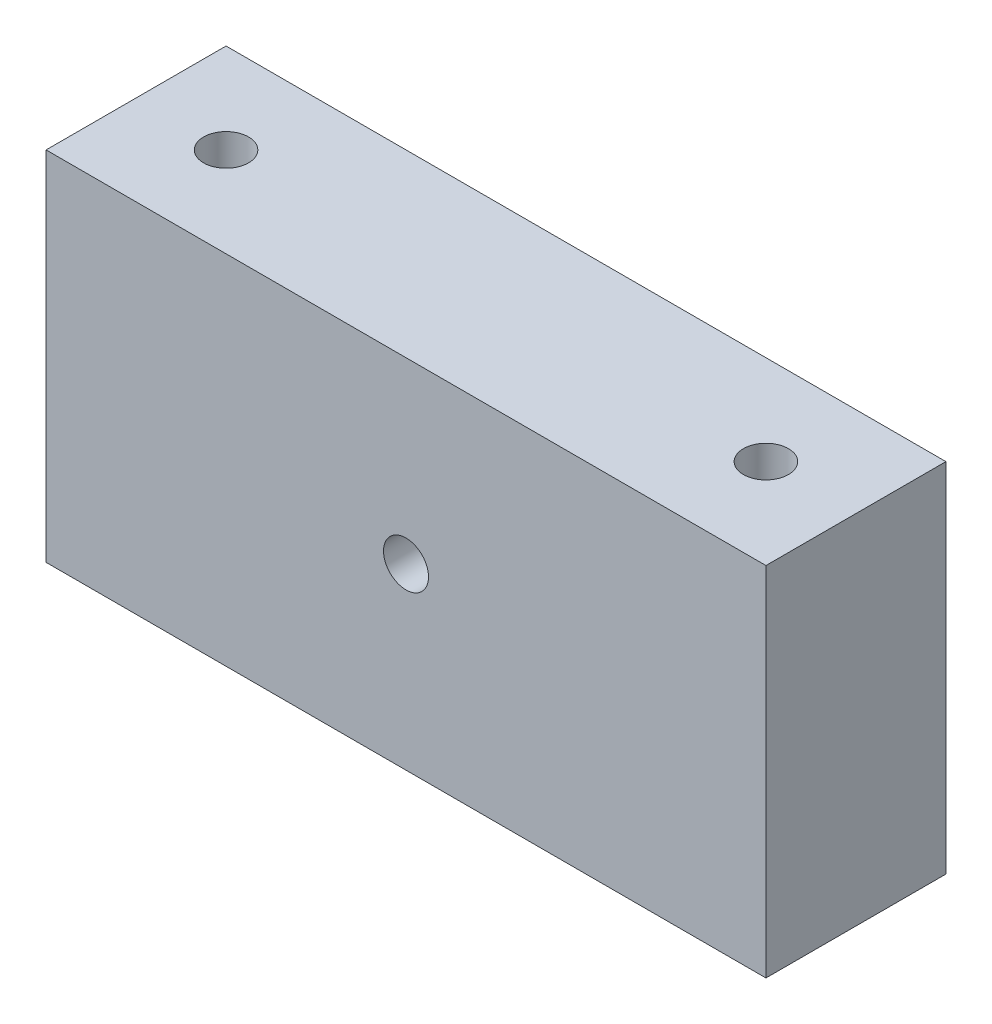
SolidWorks part; units mm, degrees
material "Copper"
ref_plane "Front Plane" through (0, 0, 0) normal (0, 0, 1) x (1, 0, 0)
ref_plane "Top Plane" through (0, 0, 0) normal (0, 1, 0) x (1, 0, 0)
ref_plane "Right Plane" through (0, 0, 0) normal (1, 0, 0) x (0, 0, -1)
sketch "Sketch1" plane through (0, 0, 0) normal (0, 1, 0) x (1, 0, 0)
  line L0 (0, 5) -> (40, 5) construction
  line L1 (0, 0) -> (40, 0)
  line L2 (0, 0) -> (0, 10)
  line L3 (0, 10) -> (40, 10)
  line L4 (40, 0) -> (40, 10)
  line L5 (5, 5) -> (5, 10) construction
  line L6 (35, 10) -> (35, 5) construction
  dimension "D1" = 5
  dimension "D2" = 5
  dimension "D3" = 5
  dimension "D4" = 5
  dimension "D5" = 40
extrude "Boss-Extrude1" add sketch "Sketch1" along normal blind 19.85
sketch "Sketch2" plane through (0, 19.85, 0) normal (0, 1, 0) x (1, 0, 0)
  point P0 (35, 5)
  point P2 (5, 5)
hole_wizard "M3x0.5 Tapped Hole3" positions "3DSketch1" profile "Sketch3" tap size "M3x0.5" standard "ANSI Metric" end condition through all
sketch3d "3DSketch1"
  point P0 (5, 19.85, -5)
  point P3 (35, 19.85, -5)
sketch "Sketch3" plane through (5, 19.85, -5) normal (1, 0, 0) x (0, 0, 1)
  line L0 (0, 0) -> (0, 19.85)
  line L1 (0, 19.85) -> (1.25, 19.85)
  line L2 (1.25, 19.85) -> (1.25, 0)
  line L5 (1.25, 0) -> (0, 0)
  line L11 (0, -6.35) -> (0, 107.95) construction
  dimension "Thru Tap Drill Dia." = 2.5
  dimension "Thru Tap Drill Depth" = 19.85
cosmetic thread "Hole Thread1" parameters "D2"=3
cosmetic thread "Hole Thread2" parameters "D2"=3
sketch "Sketch4" plane through (0, 0, -10) normal (0, 0, -1) x (-1, 0, 0)
  line L0 (-40, 9.925) -> (0, 9.925)
  line L1 (-40, 19.85) -> (-40, 0) construction
  line L2 (0, 19.85) -> (0, 0) construction
hole_wizard "M3x0.5 Tapped Hole4" positions "3DSketch2" profile "Sketch5" tap size "M3x0.5" standard "ANSI Metric" end condition through all
sketch3d "3DSketch2"
  line L0 (40, 9.925, -10) -> (0, 9.925, -10) construction
  point P0 (20, 9.925, -10)
cosmetic thread "Hole Thread3" parameters "D2"=3
sketch "Sketch5" plane through (20, 9.925, -10) normal (1, 0, 0) x (0, 1, 0)
  line L0 (0, 0) -> (0, 10)
  line L1 (0, 10) -> (1.25, 10)
  line L2 (1.25, 10) -> (1.25, 0)
  line L5 (1.25, 0) -> (0, 0)
  line L11 (0, -6.35) -> (0, 107.95) construction
  dimension "Thru Tap Drill Dia." = 2.5
  dimension "Thru Tap Drill Depth" = 10
equation "\"D2@Sketch1\"=\"D1@Sketch1\""
equation "\"D3@Sketch1\"=\"D1@Sketch1\""
